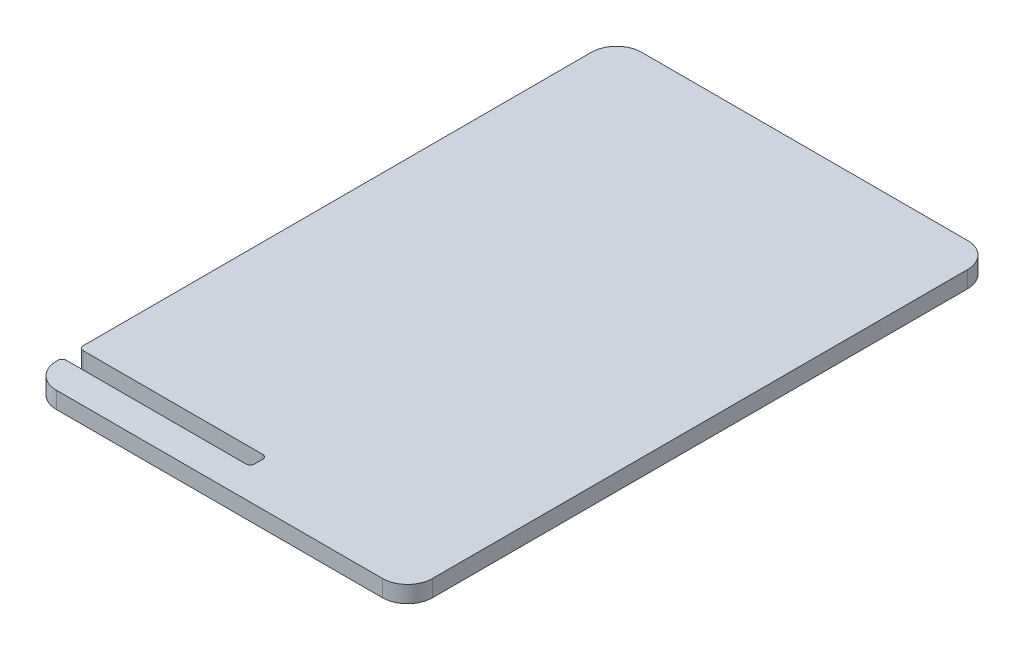
SolidWorks part; units mm, degrees
ref_plane "Alzado" through (0, 0, 0) normal (0, 0, 1) x (1, 0, 0)
ref_plane "Planta" through (0, 0, 0) normal (0, 1, 0) x (1, 0, 0)
ref_plane "Vista lateral" through (0, 0, 0) normal (1, 0, 0) x (0, 0, -1)
sketch "Croquis1" plane through (0, 0, 0) normal (0, 1, 0) x (1, 0, 0)
  line L1 (-22.5, 35.3062) -> (22.5, 35.3062)
  line L2 (-22.5, 35.3062) -> (-22.5, -34.6938)
  line L3 (-22.5, -34.6938) -> (22.5, -34.6938)
  line L4 (22.5, 35.3062) -> (22.5, -34.6938)
  dimension "D1" = 22.5
  dimension "D2" = 45
  dimension "D3" = 35.3062
  dimension "D4" = 70
extrude "Saliente-Extruir1" add sketch "Croquis1" along normal blind 2
sketch "Croquis2" plane through (0, 2, 0) normal (0, 1, 0) x (1, 0, 0)
  line L0 (-22.5, 35.3062) -> (-22.5, -34.6938) construction
  line L1 (-22.5, -29) -> (0, -29)
  line L2 (-22.5, -29) -> (-22.5, -31)
  line L3 (-22.5, -31) -> (0, -31)
  line L4 (0, -29) -> (0, -31)
  dimension "D1" = 2
  dimension "D2" = 31
  dimension "D3" = 22.5
extrude "Cortar-Extruir1" cut sketch "Croquis2" against normal up to surface (2 mm away) up to face at (0, 0, -0.3062)
fillet "Redondeo1" radius 3 4 edges at (-22.5, 1, 34.6938) (22.5, 1, 34.6938) (-22.5, 1, -35.3062) (22.5, 1, -35.3062)
fillet "Redondeo2" radius 0.5 4 edges at (-22.5, 1, 31) (0, 1, 31) (0, 1, 29) (-22.5, 1, 29)
